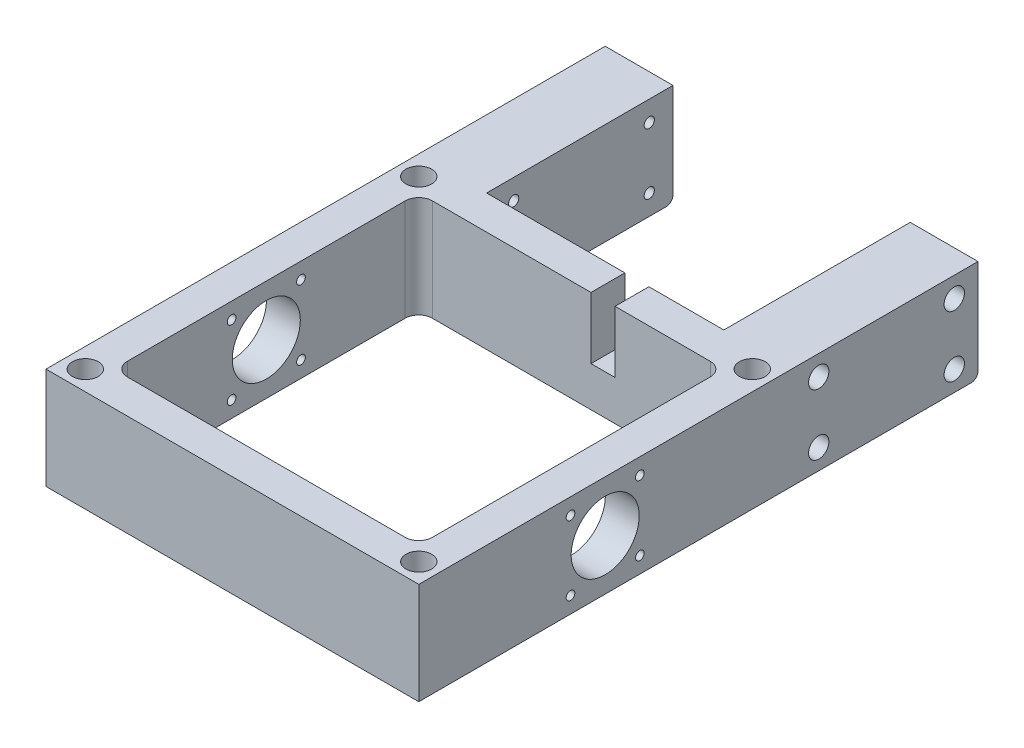
SolidWorks part; units mm, degrees
ref_plane "Front Plane" through (0, 0, 0) normal (0, 0, 1) x (1, 0, 0)
ref_plane "Top Plane" through (0, 0, 0) normal (0, 1, 0) x (1, 0, 0)
ref_plane "Right Plane" through (0, 0, 0) normal (1, 0, 0) x (0, 0, -1)
sketch "Sketch1" plane through (0, 0, 0) normal (0, 1, 0) x (1, 0, 0)
  line L1 (-69.85, 69.85) -> (69.85, 69.85)
  line L2 (-69.85, 69.85) -> (-69.85, -69.85)
  line L3 (-69.85, -69.85) -> (69.85, -69.85)
  line L4 (69.85, 69.85) -> (69.85, -69.85)
  line L5 (-69.85, 69.85) -> (69.85, -69.85) construction
  line L6 (-69.85, -69.85) -> (69.85, 69.85) construction
  line L7 (-69.85, 69.85) -> (-31.75, 69.85)
  line L31 (-69.85, 69.85) -> (-44.45, 69.85)
  line L32 (-69.85, 69.85) -> (-69.85, 139.7)
  line L33 (-69.85, 139.7) -> (-44.45, 139.7)
  line L34 (-44.45, 69.85) -> (-44.45, 139.7)
  line L35 (69.85, 69.85) -> (44.45, 69.85)
  line L36 (69.85, 69.85) -> (69.85, 139.7)
  line L37 (69.85, 139.7) -> (44.45, 139.7)
  line L38 (44.45, 69.85) -> (44.45, 139.7)
  line L39 (-57.15, 57.15) -> (57.15, 57.15)
  line L40 (-57.15, 57.15) -> (-57.15, -57.15)
  line L41 (-57.15, -57.15) -> (57.15, -57.15)
  line L42 (57.15, 57.15) -> (57.15, -57.15)
  line L43 (-57.15, 57.15) -> (57.15, -57.15) construction
  line L44 (-57.15, -57.15) -> (57.15, 57.15) construction
  circle A0 centre (-62.484, -62.484) radius 7.366 construction
  circle A1 centre (-62.484, -62.484) radius 4.826
  circle A2 centre (62.484, -62.484) radius 4.826
  circle A3 centre (62.484, -62.484) radius 7.366 construction
  circle A4 centre (-62.484, 62.484) radius 4.826
  circle A5 centre (-62.484, 62.484) radius 7.366 construction
  circle A6 centre (62.484, 62.484) radius 7.366 construction
  circle A7 centre (62.484, 62.484) radius 4.826
  point P0 (0, 0)
  point P23 (0, 0)
  dimension "D7" = 9.652
  dimension "D8" = 14.732
  dimension "D9" = 9.652
  dimension "D10" = 14.732
  dimension "D11" = 9.652
  dimension "D12" = 14.732
  dimension "D13" = 9.652
  dimension "D15" = 114.3
  dimension "D16" = 114.3
  dimension "D6" = 14.732
  dimension "D1" = 139.7
  dimension "D2" = 139.7
  dimension "D3" = 69.85
  dimension "D4" = 69.85
  dimension "D5" = 88.9
extrude "Boss-Extrude2" add sketch "Sketch1" along normal blind 38.1 contours L1 L34 L33 L32 | L4 L1 L7 L2 L3 A7 A4 A2 A1 L39 L42 L41 L40 | L1 | L35 L38 L37 L36 region at (-57.15, 0, -104.775) region at (-57.15, 0, -67.8743) region at (57.15, 0, -104.775)
sketch "Sketch5" plane through (69.85, 0, 0) normal (1, 0, 0) x (0, 0, -1)
  line L2 (139.7, 38.1) -> (-69.85, 38.1) construction
  line L3 (-13, 6.05) -> (13, 6.05) construction
  line L4 (-13, 6.05) -> (-13, 32.05) construction
  line L5 (-13, 32.05) -> (13, 32.05) construction
  line L6 (13, 6.05) -> (13, 32.05) construction
  line L7 (-13, 6.05) -> (13, 32.05) construction
  line L8 (-13, 32.05) -> (13, 6.05) construction
  circle A0 centre (0, 19.05) radius 12.75
  circle A1 centre (-13, 32.05) radius 1.6319
  circle A2 centre (13, 32.05) radius 1.6319
  circle A3 centre (13, 6.05) radius 1.632
  circle A4 centre (-13, 6.05) radius 1.632
  point P12 (0, 0)
  dimension "D1" = 25.5
  dimension "D2" = 19.05
  dimension ".1160 " = 3.2639
  dimension "D6" = 3.2639
  dimension "D7" = 3.2639
  dimension "D8" = 3.2639
  dimension "D3" = 26
  dimension "D4" = 26
extrude "Cut-Extrude1" cut sketch "Sketch5" against normal up to surface (139.7 mm away) contours A1 | A3 | A4 | A2 | A0 region at (69.85, 32.05, 13) region at (69.85, 32.05, -13) region at (69.85, 6.05, -13) region at (69.85, 6.05, 13) up to face at (-69.85, 19.05, -34.925)
ref_plane "Plane2" through (11.88, 0, 0) normal (-1, 0, 0) x (0, 0, 1)
sketch "Sketch7" plane through (11.88, 0, 0) normal (-1, 0, 0) x (0, 0, 1)
  line L0 (-69.85, 38.1) -> (-69.85, 0) construction
  line L1 (-57.15, 38.1) -> (-57.15, 0) construction
  line L2 (-69.85, 38.1) -> (-69.85, 15)
  line L3 (-57.15, 38.1) -> (-57.15, 15)
  line L4 (-69.85, 38.1) -> (-57.15, 38.1)
  line L5 (-69.85, 15) -> (-57.15, 15)
  line L6 (69.85, 0) -> (-139.7, 0) construction
  point P1 (-57.15, 14.5116)
  point P8 (-69.85, 14.5116)
  dimension "D1" = 15
extrude "Cut-Extrude2" cut sketch "Sketch7" against normal mid plane 9 contours L4 L3 L5 L2
sketch "Sketch10" plane through (69.85, 0, 0) normal (1, 0, 0) x (0, 0, -1)
  line L0 (139.7, 38.1) -> (139.7, 0) construction
  line L1 (130.81, 7.62) -> (80.01, 7.62) construction
  line L2 (130.81, 7.62) -> (130.81, 30.48) construction
  line L3 (130.81, 30.48) -> (80.01, 30.48) construction
  line L4 (80.01, 7.62) -> (80.01, 30.48) construction
  line L5 (139.7, 0) -> (-69.85, 0) construction
  circle A0 centre (80.01, 30.48) radius 1.905
  circle A1 centre (80.01, 30.48) radius 3.81
  circle A2 centre (130.81, 30.48) radius 1.905
  circle A3 centre (130.81, 7.62) radius 1.905
  circle A4 centre (130.81, 7.62) radius 3.81
  circle A5 centre (130.81, 30.48) radius 3.81
  circle A6 centre (80.01, 7.62) radius 1.905
  circle A7 centre (80.01, 7.62) radius 3.81
  point P16 (0, 0)
  dimension "D5" = 3.81
  dimension "D6" = 3.81
  dimension "D7" = 3.81
  dimension "D8" = 3.81
  dimension "D9" = 7.62
  dimension "D10" = 7.62
  dimension "D11" = 7.62
  dimension "D12" = 7.62
  dimension "D1" = 8.89
  dimension "D2" = 7.62
  dimension "D3" = 22.86
  dimension "D4" = 50.8
extrude "Cut-Extrude3" cut sketch "Sketch10" against normal up to surface (139.7 mm away) contours A0 | A6 | A2 | A3 region at (69.85, 30.48, -80.01) region at (69.85, 7.62, -80.01) up to face at (-69.85, 6.05, -11.3681)
extrude "Cut-Extrude4" cut sketch "Sketch10<3>" against normal blind 15.24
sketch "Sketch10<3>" plane through (69.85, 0, 0) normal (1, 0, 0) x (0, 0, -1) same geometry as "Sketch10"
sketch "Sketch11" plane through (-69.85, 0, 0) normal (-1, 0, 0) x (0, 0, 1)
  line L0 (-80.01, 7.62) -> (-130.81, 7.62) construction
  line L1 (-80.01, 7.62) -> (-80.01, 30.48) construction
  line L2 (-80.01, 30.48) -> (-130.81, 30.48) construction
  line L3 (-130.81, 7.62) -> (-130.81, 30.48) construction
  circle A0 centre (-130.81, 30.48) radius 3.81
  circle A1 centre (-80.01, 7.62) radius 3.81
  circle A2 centre (-80.01, 30.48) radius 3.81
  circle A3 centre (-130.81, 7.62) radius 3.81
  point P8 (-130.81, 30.48)
  point P10 (-130.81, 7.62)
  point P12 (-80.01, 7.62)
  dimension "D1" = 7.62
  dimension "D2" = 7.62
  dimension "D3" = 7.62
  dimension "D4" = 7.62
extrude "Cut-Extrude5" cut sketch "Sketch11" against normal blind 15.24
fillet "Fillet10" radius 5.08 1 edges at (57.15, 19.05, -57.15)
fillet "Fillet11" radius 5.08 1 edges at (-57.15, 19.05, -57.15)
fillet "Fillet12" radius 5.08 1 edges at (-57.15, 19.05, 57.15)
fillet "Fillet13" radius 5.08 1 edges at (57.15, 19.05, 57.15)
fillet "Fillet16" radius 2.54 1 edges at (-57.15, 0, -139.7)
fillet "Fillet17" radius 2.54 1 edges at (57.15, 0, -139.7)
equation "\"D1@Plane2\"=(8.3mm/2)+41.12mm"
